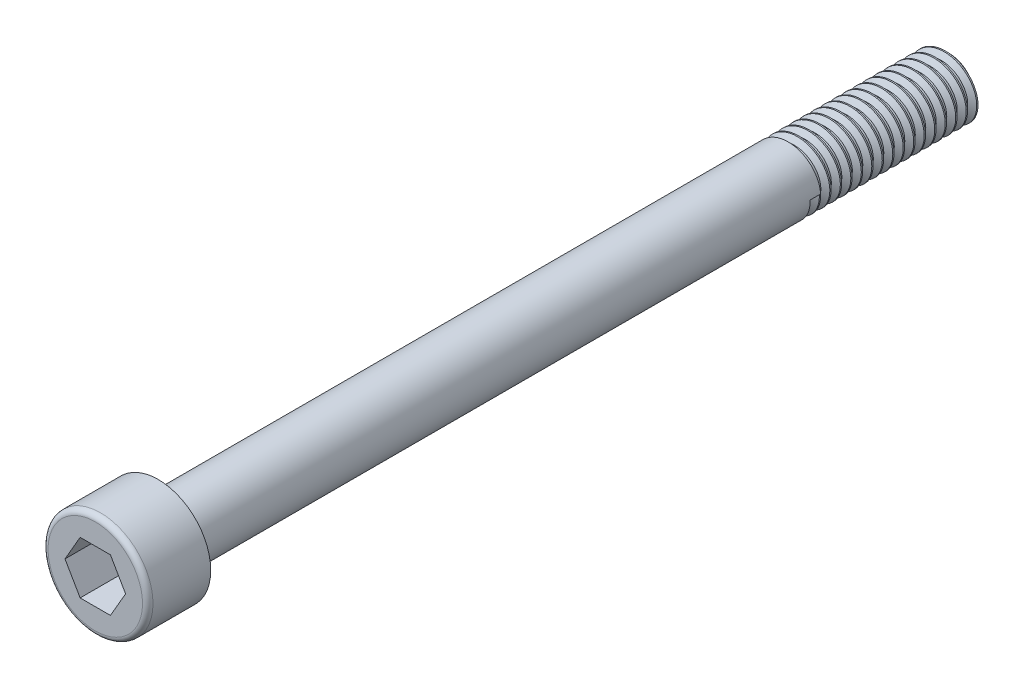
SolidWorks part; units mm, degrees
material "Gri Dökme Demir"
ref_plane "Ön Düzlem" through (0, 0, 0) normal (0, 0, 1) x (1, 0, 0)
ref_plane "Üst Düzlem" through (0, 0, 0) normal (0, 1, 0) x (1, 0, 0)
ref_plane "Sağ Düzlem" through (0, 0, 0) normal (1, 0, 0) x (0, 0, -1)
sketch "Çizim1" plane through (0, 0, 0) normal (0, 0, 1) x (1, 0, 0)
  circle A0 centre (0, 0) radius 3
  dimension "D1" = 6
extrude "Yükseklik-Ekstrüzyon1" add sketch "Çizim1" along normal blind 90
thread "Diş1" pitch 1 method cut trim with start face yes profile "Diş Profili1" start angle 0, offset 1, length 25, pitch 1, diameter 6
ref_plane "Düzlem1" through (3, 0, -1) normal (0, -1, 0) x (1, 0, 0)
sketch "Diş Profili1" plane through (3, 0, -1) normal (0, -1, 0) x (1, 0, 0)
  line L0 (0, 0) -> (0, 1) construction
  line L11 (0, 0) -> (0, 0.875)
  line L12 (0, 0.875) -> (-0.5413, 0.5625)
  line L13 (-0.5413, 0.5625) -> (-0.5413, 0.3125)
  line L15 (-0.5413, 0.3125) -> (0, 0)
  line L17 (-0.5413, 0.4375) -> (0, 0.4375) construction
  point P2 (0, 0)
  dimension "Pitch" = 1
  dimension "Profile_Angle" = 60
  dimension "Profile_Land" = 0.25
  dimension "Profile_Height" = 0.5413
sketch "Çizim5" plane through (0, 0, 90) normal (0, 0, 1) x (1, 0, 0)
  circle A0 centre (0, 0) radius 5
  dimension "D1" = 10
extrude "Yükseklik-Ekstrüzyon2" add sketch "Çizim5" against normal blind 6
sketch "Çizim6" plane through (0, 0, 90) normal (0, 0, 1) x (1, 0, 0)
  line L1 (2.8868, 0) -> (1.4434, 2.5)
  line L2 (1.4434, 2.5) -> (-1.4434, 2.5)
  line L3 (-1.4434, 2.5) -> (-2.8868, 0)
  line L4 (-2.8868, 0) -> (-1.4434, -2.5)
  line L5 (-1.4434, -2.5) -> (1.4434, -2.5)
  line L6 (1.4434, -2.5) -> (2.8868, 0)
  circle A0 centre (0, 0) radius 2.5 construction
  dimension "D1" = 5
extrude "Kes-Ekstrüzyon1" cut sketch "Çizim6" against normal blind 5
fillet "Radyus1" radius 0.5 7 edges at (5, 0, 90) (0, -2.5, 85) (-2.1651, -1.25, 85) (-2.1651, 1.25, 85) (0, 2.5, 85) (2.1651, 1.25, 85) (2.1651, -1.25, 85)
sketch "Çizim7" plane through (0, 0, 0) normal (0, 0, -1) x (-1, 0, 0)
  line L1 (-8.395, 5.19) -> (8.395, 5.19)
  line L2 (-8.395, 5.19) -> (-8.395, -5.19)
  line L3 (-8.395, -5.19) -> (8.395, -5.19)
  line L4 (8.395, 5.19) -> (8.395, -5.19)
  line L5 (-8.395, 5.19) -> (8.395, -5.19) construction
  line L6 (-8.395, -5.19) -> (8.395, 5.19) construction
  point P0 (0, 0)
extrude "Kes-Ekstrüzyon2" cut sketch "Çizim7" against normal blind 8.6
